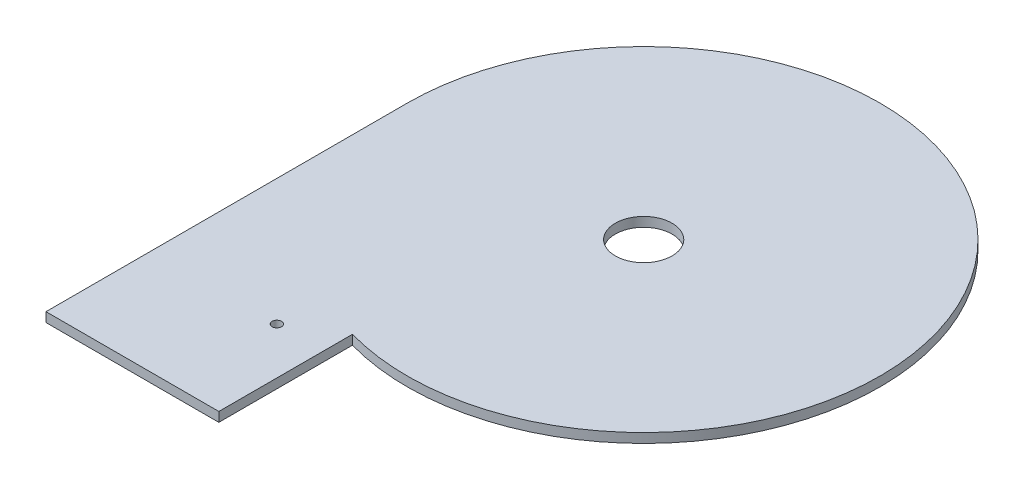
SolidWorks part; units mm, degrees
ref_plane "Front Plane" through (0, 0, 0) normal (0, 0, 1) x (1, 0, 0)
ref_plane "Top Plane" through (0, 0, 0) normal (0, 1, 0) x (1, 0, 0)
ref_plane "Right Plane" through (0, 0, 0) normal (1, 0, 0) x (0, 0, -1)
sketch "Sketch1" plane through (0, 0, 0) normal (0, 1, 0) x (1, 0, 0)
  circle A0 centre (0, 0) radius 50
extrude "Boss-Extrude1" add sketch "Sketch1" along normal blind 2
sketch "Sketch2" plane through (0, 2, 0) normal (0, 1, 0) x (1, 0, 0)
  circle A0 centre (0, 0) radius 6
extrude "Cut-Extrude1" cut sketch "Sketch2" against normal blind 2
sketch "Sketch3" plane through (0, 0, 0) normal (0, -1, 0) x (1, 0, 0)
  line L1 (-50, 0) -> (-13.4445, 0)
  line L2 (-50, 0) -> (-50, 76.4199)
  line L3 (-50, 76.4199) -> (-13.4445, 76.4199)
  line L4 (-13.4445, 0) -> (-13.4445, 76.4199)
  circle A0 centre (0, 0) radius 50 construction
extrude "Boss-Extrude2" add sketch "Sketch3" against normal through all
sketch "Sketch4" plane through (0, 2, 0) normal (0, 1, 0) x (1, 0, 0)
  line L4 (-26, -48.23) -> (-26, -61.13)
  line L5 (-20.1, -48.23) -> (-26, -48.23)
  line L6 (-20.1, -61.13) -> (-20.1, -48.23)
  line L7 (-26, -61.13) -> (-20.1, -61.13)
  line L8 (-26, -48.23) -> (-26, -61.13)
  line L9 (-20.1, -48.23) -> (-26, -48.23)
  line L10 (-20.1, -61.13) -> (-20.1, -48.23)
  line L11 (-26, -61.13) -> (-20.1, -61.13)
  dimension "D1" = 0
sketch "Sketch5" plane through (0, 0, 0) normal (0, -1, 0) x (1, 0, 0)
  circle A0 centre (-23.3202, 54.2741) radius 1 construction
  circle A1 centre (-23.3202, 54.2741) radius 1
extrude "Cut-Extrude2" cut sketch "Sketch5" against normal up to next
